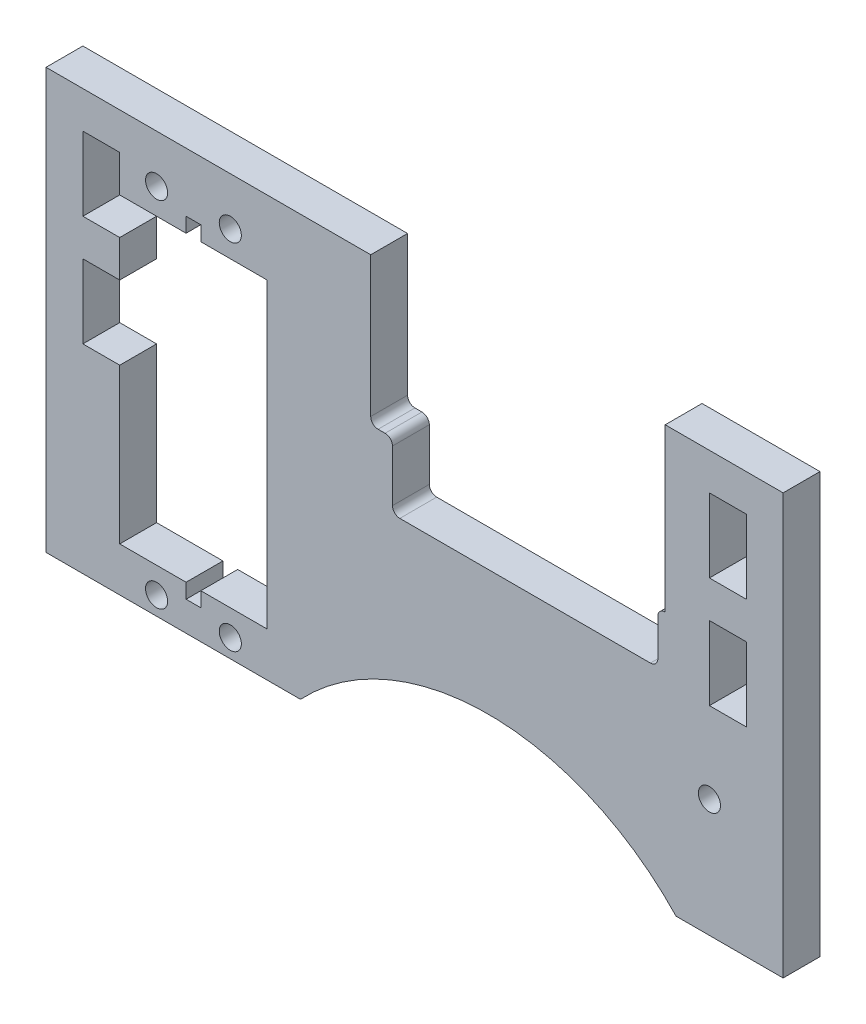
SolidWorks part; units mm, degrees
ref_plane "Plan de face" through (0, 0, 0) normal (0, 0, 1) x (1, 0, 0)
ref_plane "Plan de dessus" through (0, 0, 0) normal (0, 1, 0) x (1, 0, 0)
ref_plane "Plan de droite" through (0, 0, 0) normal (1, 0, 0) x (0, 0, -1)
sketch "Esquisse1" plane through (0, 0, 0) normal (0, 0, 1) x (1, 0, 0)
  line L0 (20, 67) -> (20, -4) construction
  line L1 (0, 0) -> (34.5245, 0)
  line L2 (0, 0) -> (0, 57)
  line L3 (0, 57) -> (44.05, 57)
  line L4 (100, 0) -> (100, 57)
  line L5 (10, 26.5) -> (30, 26.5) construction
  line L6 (10, 47) -> (19, 47)
  line L7 (10, 42) -> (10, 37)
  line L8 (10, 6) -> (19, 6)
  line L9 (30, 47) -> (30, 6)
  line L10 (20, 16) -> (90, 16) construction
  line L11 (85.4755, 0) -> (100, 0)
  line L12 (21, 4) -> (21, 6)
  line L13 (19, 49) -> (21, 49)
  line L14 (19, 49) -> (19, 47)
  line L15 (21, 6) -> (30, 6)
  line L16 (21, 49) -> (21, 47)
  line L17 (19, 4) -> (21, 4)
  line L18 (19, 4) -> (19, 6)
  line L19 (21, 47) -> (30, 47)
  line L20 (10, 27) -> (10, 6)
  line L21 (90, 52) -> (95, 52)
  line L22 (90, 52) -> (90, 42)
  line L23 (90, 42) -> (95, 42)
  line L24 (95, 52) -> (95, 42)
  line L25 (90, 37) -> (95, 37)
  line L26 (90, 37) -> (90, 27)
  line L27 (90, 27) -> (95, 27)
  line L28 (95, 37) -> (95, 27)
  line L29 (5, 52) -> (10, 52)
  line L30 (5, 52) -> (5, 42)
  line L31 (5, 42) -> (10, 42)
  line L32 (10, 52) -> (10, 47)
  line L33 (5, 37) -> (10, 37)
  line L34 (5, 37) -> (5, 27)
  line L35 (5, 27) -> (10, 27)
  line L36 (84, 57) -> (100, 57)
  line L37 (47, 37) -> (44.05, 37)
  line L38 (84, 57) -> (84, 35)
  line L39 (84, 35) -> (83, 35)
  line L40 (44.05, 57) -> (44.05, 37)
  line L42 (83, 35) -> (83, 28)
  line L43 (83, 28) -> (47, 28)
  line L44 (47, 37) -> (47, 28)
  circle A0 centre (15, 2.5) radius 1.5
  circle A1 centre (25, 2.5) radius 1.5
  circle A2 centre (25, 50.5) radius 1.5
  circle A3 centre (15, 50.5) radius 1.5
  circle A4 centre (20, 16) radius 1.5 construction
  circle A5 centre (20, 16) radius 1.5 construction
  circle A6 centre (90, 16) radius 1.5
  circle A7 centre (60, -24) radius 35 construction
  arc A8 (34.5245, 0) -> (85.4755, 0) centre (60, -24) cw
  dimension "D6" = 3.5
  dimension "D8" = 3
  dimension "D9" = 3
  dimension "D10" = 70
  dimension "D13" = 70
  dimension "D16" = 2
  dimension "D1" = 6
  dimension "D2" = 41
  dimension "D3" = 20
  dimension "D4" = 10
  dimension "D5" = 100
  dimension "D7" = 5
  dimension "D11" = 10
  dimension "D12" = 10
  dimension "D14" = 40
  dimension "D15" = 40
  dimension "D17" = 2
  dimension "D18" = 5
  dimension "D19" = 5
  dimension "D20" = 10
  dimension "D21" = 5
  dimension "D22" = 5
  dimension "D23" = 5
  dimension "D24" = 10
  dimension "D25" = 6
  dimension "D26" = 20
  dimension "D27" = 40
  dimension "D28" = 1
  dimension "D29" = 36
  dimension "D30" = 9
  dimension "D31" = 22
  dimension "D32" = 7
extrude "Boss.-Extru.1" add sketch "Esquisse1" along normal blind 5
fillet "Congé1" radius 1 5 edges at (83, 35, 2.5) (83, 28, 2.5) (47, 28, 2.5) (47, 37, 2.5) (44.05, 37, 2.5)
